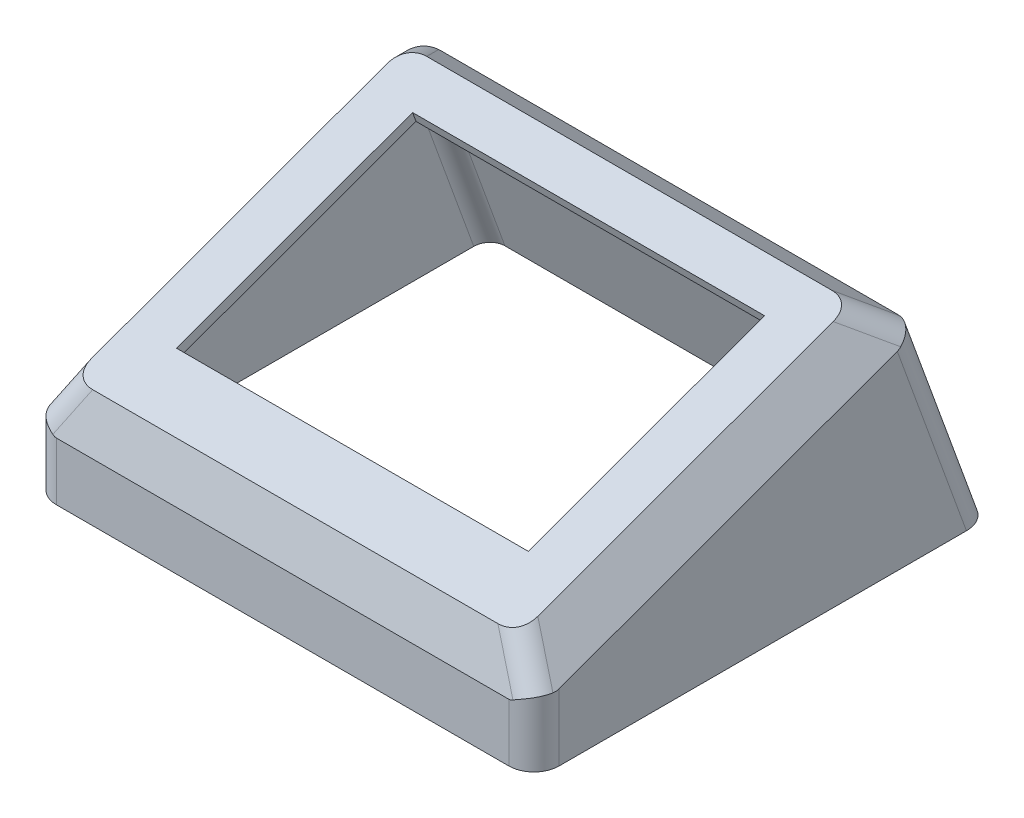
SolidWorks part; units mm, degrees
ref_plane "Front Plane" through (0, 0, 0) normal (0, 0, 1) x (1, 0, 0)
ref_plane "Top Plane" through (0, 0, 0) normal (0, 1, 0) x (1, 0, 0)
ref_plane "Right Plane" through (0, 0, 0) normal (1, 0, 0) x (0, 0, -1)
sketch "Sketch2" plane through (0, 0, 0) normal (1, 0, 0) x (0, 0, -1)
  line L0 (-74.2357, 0) -> (-74.2357, 20)
  line L1 (55, 0) -> (-55, 0) construction
  line L2 (-74.2357, 20) -> (0, 47.0196)
  line L3 (0, 55) -> (0, -55) construction
  line L4 (0, 47.0196) -> (17.1137, 0)
  line L5 (17.1137, 0) -> (-74.2357, 0)
  dimension "D1" = 79
  dimension "D2" = 20
  dimension "D3" = 110
extrude "Boss-Extrude1" add sketch "Sketch2" along normal blind 50 and the other way blind 50
chamfer "Chamfer3" distance 8 angle 35 3 edges at (50, 33.5098, 37.1179) (0, 47.0196, 0) (-50, 33.5098, 37.1179) first distance on face at (50, 16.7549, 32.8394) first distance on face at (0, 23.5098, -8.5569) first distance on face at (-50, 16.7549, 32.8394)
chamfer "Chamfer4" distance 8.5 angle 15 1 edges at (0, 20, 74.2357) first distance on face at (0, 10.4955, 74.2357)
fillet "Fillet7" radius 5 8 edges at (-50, 19.751, -9.9249) (50, 19.751, -9.9249) (-50, 5.7433, 74.2357) (50, 5.7433, 74.2357) (-47.1992, 42.3029, 1.2638) (-47.1948, 16.2093, 72.9739) (47.1992, 42.3029, 1.2638) (47.1948, 16.2093, 72.9739)
shell "Shell1" thickness 2 removed face at (0, 0, 28.6246)
sketch "Sketch3" plane through (0, 41.5193, 15.1118) normal (0, 0.9397, 0.342) x (1, 0, 0)
  line L0 (0, -55) -> (0, 55) construction
  line L1 (35, -48.157) -> (-35, -48.157)
  line L2 (35, -48.157) -> (35, 1.843)
  line L3 (35, 1.843) -> (-35, 1.843)
  line L4 (-35, -48.157) -> (-35, 1.843)
  line L5 (35, -48.157) -> (-35, 1.843) construction
  line L6 (35, 1.843) -> (-35, -48.157) construction
  point P0 (0, -23.157)
  dimension "D1" = 70
  dimension "D2" = 50
extrude "Cut-Extrude1" cut sketch "Sketch3" against normal up to surface (2 mm away) up to face at (0, 31.1317, 37.8039)
